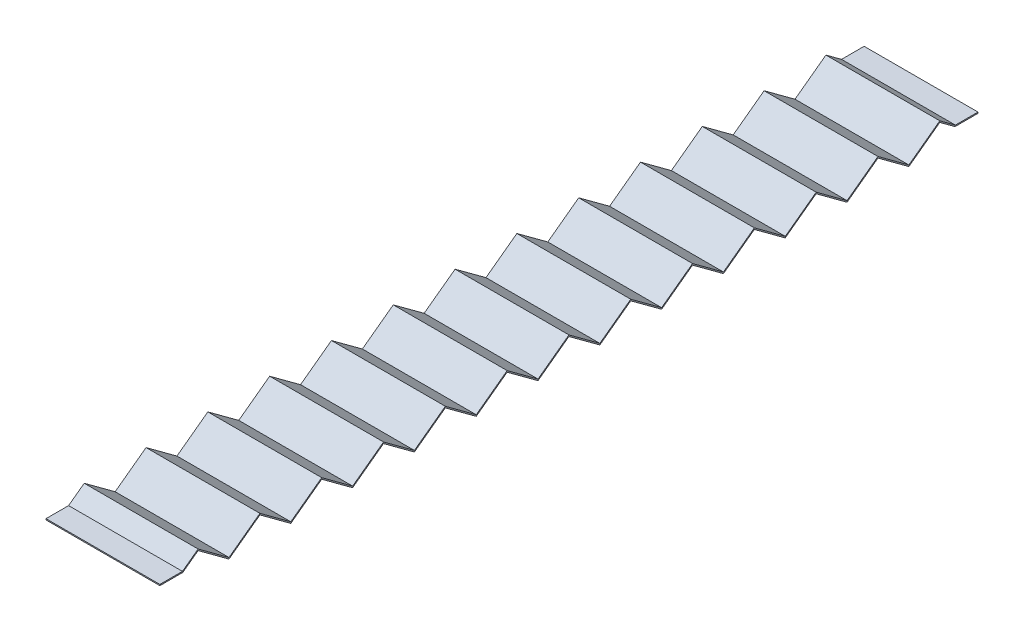
SolidWorks part; units mm, degrees
ref_plane "Front Plane" through (0, 0, 0) normal (0, 0, 1) x (1, 0, 0)
ref_plane "Top Plane" through (0, 0, 0) normal (0, 1, 0) x (1, 0, 0)
ref_plane "Right Plane" through (0, 0, 0) normal (1, 0, 0) x (0, 0, -1)
sketch "Sketch2" plane through (0, 0, 0) normal (0, 0, 1) x (1, 0, 0)
  line L1 (-27.5, 10) -> (27.5, 10)
  line L2 (-27.5, 10) -> (-27.5, 0)
  line L3 (-27.5, 0) -> (27.5, 0)
  line L4 (27.5, 10) -> (27.5, 0)
  point P4 (0, 0)
  dimension "D1" = 10
  dimension "D2" = 55
sketch "Sketch3" plane through (0, 0, 0) normal (1, 0, 0) x (0, 0, -1)
  line L0 (0, 10) -> (359.2315, 10) construction
  line L1 (0, 0) -> (359.2315, 0) construction
  line L3 (10, 5) -> (16.7846, 10)
  line L4 (16.7846, 10) -> (30.3539, 0)
  line L5 (30.3539, 0) -> (43.9231, 10)
  line L6 (43.9231, 10) -> (57.4924, 0)
  line L7 (57.4924, 0) -> (71.0617, 10)
  line L8 (71.0617, 10) -> (84.6309, 0)
  line L9 (84.6309, 0) -> (98.2002, 10)
  line L10 (98.2002, 10) -> (111.7694, 0)
  line L11 (111.7694, 0) -> (125.3387, 10)
  line L12 (125.3387, 10) -> (138.908, 0)
  line L13 (138.908, 0) -> (152.4772, 10)
  line L14 (152.4772, 10) -> (166.0465, 0)
  line L15 (166.0465, 0) -> (179.6157, 10)
  line L16 (179.6157, 10) -> (193.185, 0)
  line L17 (193.185, 0) -> (206.7543, 10)
  line L18 (206.7543, 10) -> (220.3235, 0)
  line L19 (0, 10) -> (0, 0) construction
  line L20 (220.3235, 0) -> (233.8928, 10)
  line L21 (233.8928, 10) -> (247.462, 0)
  line L22 (247.462, 0) -> (261.0313, 10)
  line L23 (261.0313, 10) -> (274.6006, 0)
  line L24 (274.6006, 0) -> (288.1698, 10)
  line L25 (288.1698, 10) -> (301.7391, 0)
  line L26 (301.7391, 0) -> (315.3083, 10)
  line L27 (315.3083, 10) -> (328.8776, 0)
  line L28 (328.8776, 0) -> (342.4468, 10)
  line L29 (342.4468, 10) -> (349.2315, 5)
  line L30 (359.2315, 10) -> (359.2315, 0) construction
  line L31 (10, 5) -> (0, 5)
  line L32 (349.2315, 5) -> (359.2315, 5)
  line L33 (359.2315, -12.3958) -> (359.2315, -19.8536) construction
  dimension "D2" = 10
  dimension "D1" = 10
  dimension "D3" = 10
extrude "Extrude-Thin1" add sketch "Sketch3" against normal mid plane 50 thin thin type mid plane wall 0.5
